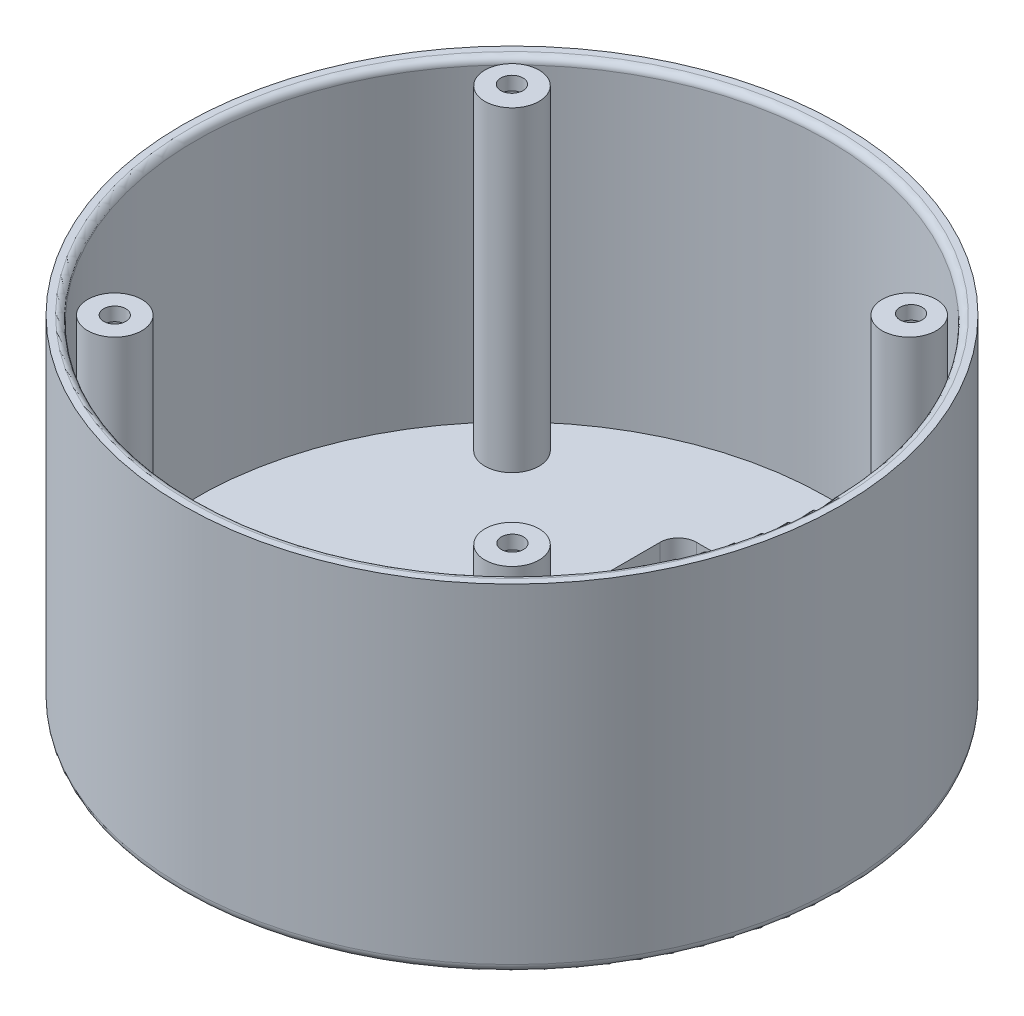
SolidWorks part; units mm, degrees
ref_plane "Front Plane" through (0, 0, 0) normal (0, 0, 1) x (1, 0, 0)
ref_plane "Top Plane" through (0, 0, 0) normal (0, 1, 0) x (1, 0, 0)
ref_plane "Right Plane" through (0, 0, 0) normal (1, 0, 0) x (0, 0, -1)
sketch "Sketch2" plane through (0, 0, 0) normal (0, 1, 0) x (1, 0, 0)
  circle A0 centre (0, 0) radius 36.5
extrude "Boss-Extrude1" add sketch "Sketch2" along normal blind 2.5
sketch "Sketch3" plane through (0, 2.5, 0) normal (0, 1, 0) x (1, 0, 0)
  circle A0 centre (0, 0) radius 36.5
  circle A1 centre (0, 0) radius 35
extrude "Boss-Extrude2" add sketch "Sketch3" along normal blind 35
sketch "Sketch4" plane through (0, 2.5, 0) normal (0, 1, 0) x (1, 0, 0)
  line L7 (-22, 22) -> (22, -22) construction
  line L8 (-22, -22) -> (22, 22) construction
  circle A0 centre (-22, 22) radius 3
  circle A1 centre (22, 22) radius 3
  circle A2 centre (22, -22) radius 3
  circle A3 centre (-22, -22) radius 3
extrude "Boss-Extrude3" add sketch "Sketch4" along normal blind 35
sketch "Sketch5" plane through (0, 37.5, 0) normal (0, 1, 0) x (1, 0, 0)
  line L5 (22, -22) -> (-22, 22) construction
  line L6 (22, 22) -> (-22, -22) construction
  circle A0 centre (-22, -22) radius 1.225
  circle A1 centre (-22.145, 22.1354) radius 1.225
  circle A2 centre (21.9598, 22.2466) radius 1.225
  circle A3 centre (21.9042, -21.8582) radius 1.225
  point P0 (0, 0)
extrude "Cut-Extrude2" cut sketch "Sketch5" against normal through all
sketch "Sketch9" plane through (0, 0, 0) normal (0, -1, 0) x (1, 0, 0)
  line L1 (-22, 22) -> (22, 22)
  line L2 (-22, 22) -> (-22, -22)
  line L3 (-22, -22) -> (22, -22)
  line L4 (22, 22) -> (22, -22)
  line L5 (-22, 22) -> (22, -22) construction
  line L6 (-22, -22) -> (22, 22) construction
  circle A0 centre (22, 22) radius 2.5
  circle A1 centre (22, -22) radius 2.5
  circle A2 centre (-22, -22) radius 2.5
  circle A3 centre (-22, 22) radius 2.5
  point P0 (0, 0)
  circle M1 centre (-22.145, -22.1354) radius 1.225
  circle M2 centre (21.9598, -22.2466) radius 1.225
  circle M3 centre (21.9042, 21.8582) radius 1.225
  circle M4 centre (-22, 22) radius 1.225
extrude "Cut-Extrude7" cut sketch "Sketch9" against normal blind 36 contours L4 A0 L1 M3 | L1 A0 L4 M3 | L3 A1 L4 M2 | L4 A1 L3 M2 | L2 A2 L3 M1 | L1 A3 L2 M4 | L2 A3 L1 M4 | L3 A2 L2 M1 region at (-22.9162, 0, 22.9162) region at (-20.768, 0, 20.768) region at (22, 0, 24.4293) region at (20.7292, 0, 20.7371) region at (-20.8078, 0, -20.8085) region at (-22.0707, 0, -20.2095) region at (23.7178, 0, -20.2822) region at (20.8118, 0, -20.7898)
fillet "Fillet2" radius 0.75 1 edges at (0, 37.5, 35)
sketch "Sketch17" plane through (0, 0, 0) normal (0, -1, 0) x (1, 0, 0)
  line L1 (-5, -23.419) -> (5, -23.419)
  line L2 (-5, -23.419) -> (-5, -13.419)
  line L3 (-5, -13.419) -> (5, -13.419)
  line L4 (5, -23.419) -> (5, -13.419)
  line L5 (-5, -23.419) -> (5, -13.419) construction
  line L6 (-5, -13.419) -> (5, -23.419) construction
  point P0 (0, -18.419)
extrude "Cut-Extrude9" cut sketch "Sketch17" against normal blind 10
fillet "Fillet3" radius 2 1 edges at (5, 1.25, -13.419)
fillet "Fillet4" radius 2 1 edges at (-5, 1.25, -23.419)
fillet "Fillet5" radius 2 1 edges at (5, 1.25, -23.419)
fillet "Fillet6" radius 2 1 edges at (-5, 1.25, -13.419)
sketch "Sketch18" plane through (0, 0, 0) normal (0, -1, 0) x (1, 0, 0)
  circle A0 centre (0, 0) radius 1.25
  circle A1 centre (2.8284, -2.8284) radius 1.25
  circle A2 centre (5.6569, -5.6569) radius 1.25
  circle A3 centre (8.4853, -8.4853) radius 1.25
  circle A4 centre (2.8284, 2.8284) radius 1.25
  circle A5 centre (5.6569, 5.6569) radius 1.25
  circle A6 centre (8.4853, 8.4853) radius 1.25
  circle A7 centre (-2.8284, 2.8284) radius 1.25
  circle A8 centre (-5.6569, 5.6569) radius 1.25
  circle A9 centre (-8.4853, 8.4853) radius 1.25
  circle A10 centre (-2.8284, -2.8284) radius 1.25
  circle A11 centre (-5.6569, -5.6569) radius 1.25
  circle A12 centre (-8.4853, -8.4853) radius 1.25
  dimension "D1" = 4
  dimension "D2" = 4
  dimension "D3" = 4
  dimension "D4" = 4
extrude "Cut-Extrude10" cut sketch "Sketch18" against normal blind 10
fillet "Fillet7" radius 1 1 edges at (0, 0, 36.5)
